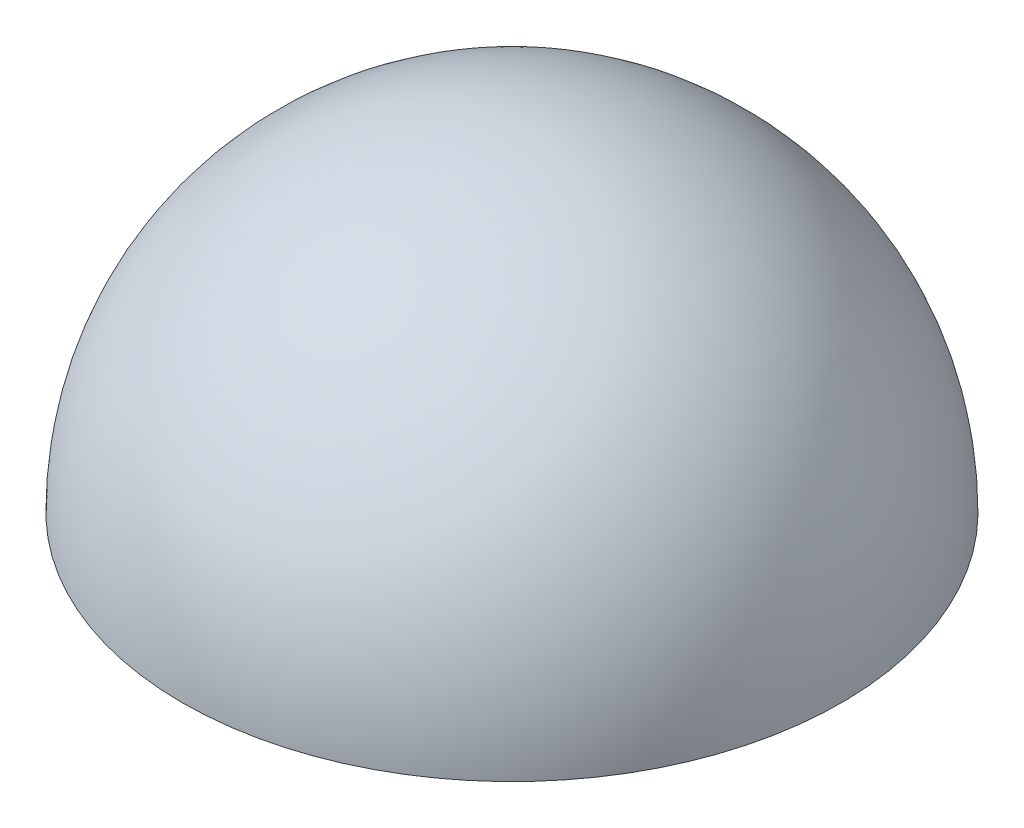
SolidWorks part; units mm, degrees
ref_plane "Front" through (0, 0, 0) normal (0, 0, 1) x (1, 0, 0)
ref_plane "Top" through (0, 0, 0) normal (0, 1, 0) x (1, 0, 0)
ref_plane "Right" through (0, 0, 0) normal (1, 0, 0) x (0, 0, -1)
ref_axis "Center Axis" through (0, 0, -88.99) along (0, 0, 1)
sketch "Sketch1" plane through (0, 0, 0) normal (0, 1, 0) x (1, 0, 0)
  line L0 (0, -19.05) -> (0, 19.05)
  arc A0 (0, 19.05) -> (0, -19.05) centre (0, 0) ccw
  dimension "D1" = 38.1
revolve "Revolve3" add sketch "Sketch1" angle 180 about L0
sketch "Sketch2" plane through (0, 0, 0) normal (0, -1, 0) x (1, 0, 0)
  line L0 (-12.7, 0) -> (12.7, 0)
  arc A0 (12.7, 0) -> (-12.7, 0) centre (0, 0) ccw
  dimension "D1" = 12.7
revolve "Cut-Revolve1" cut sketch "Sketch2" angle 180 about L0 reverse direction yes
